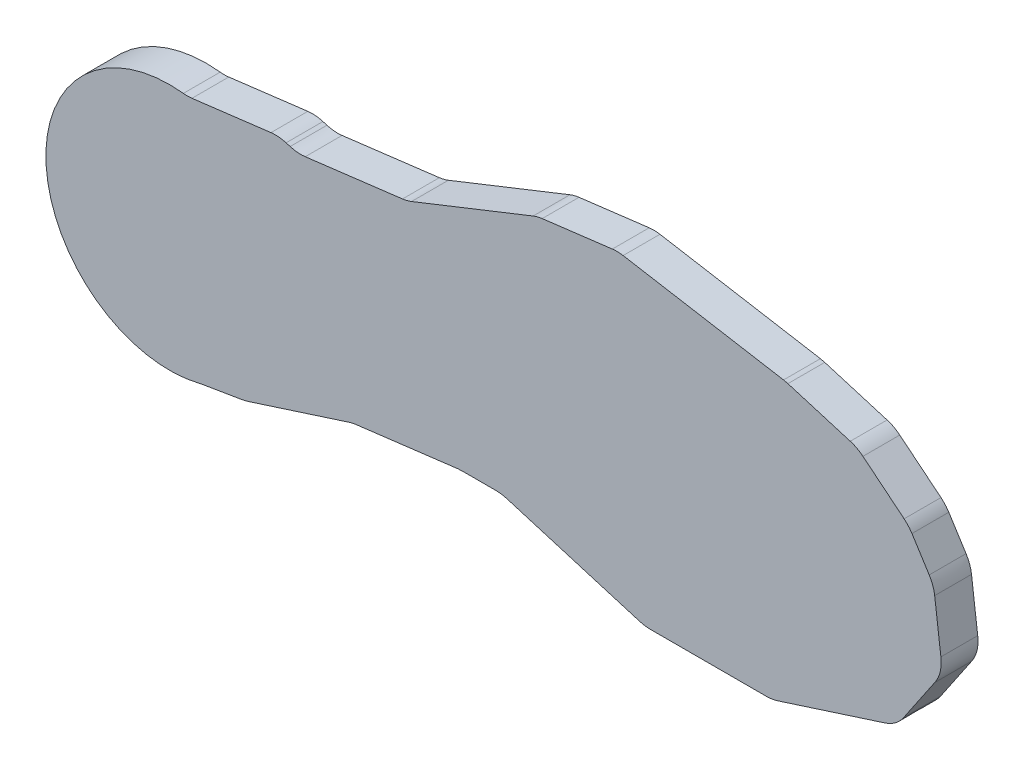
SolidWorks part; units mm, degrees
ref_plane "Front Plane" through (0, 0, 0) normal (0, 0, 1) x (1, 0, 0)
ref_plane "Top Plane" through (0, 0, 0) normal (0, 1, 0) x (1, 0, 0)
ref_plane "Right Plane" through (0, 0, 0) normal (1, 0, 0) x (0, 0, -1)
sketch "Sketch1" plane through (0, 0, 0) normal (0, 0, 1) x (1, 0, 0)
  line L0 (45.8333, 91.5) -> (229.1667, 91.5) construction
  line L1 (52.493, 111.603) -> (77.2786, 114.6756)
  line L2 (77.2786, 114.6756) -> (82.3996, 113.1393)
  line L3 (82.3996, 113.1393) -> (112.1645, 116.8292)
  line L4 (112.1645, 116.8292) -> (147.5386, 130.8579)
  line L5 (147.5386, 130.8579) -> (169.3248, 133.5587)
  line L6 (169.3248, 133.5587) -> (214.9309, 125.7369)
  line L7 (214.9309, 125.7369) -> (234.3436, 119.9131)
  line L8 (234.3436, 119.9131) -> (248.3197, 108.5304)
  line L9 (248.3197, 108.5304) -> (255.0794, 97.8788)
  line L10 (255.0794, 97.8788) -> (257.5, 78.353)
  line L11 (257.5, 78.353) -> (245.0423, 59.9834)
  line L12 (245.0423, 59.9834) -> (211.2437, 49.1269)
  line L13 (211.2437, 49.1269) -> (176.6924, 49.1269)
  line L14 (176.6924, 49.1269) -> (137.7306, 60.8155)
  line L15 (137.7306, 60.8155) -> (126.4401, 60.8155)
  line L16 (126.4401, 60.8155) -> (97.282, 57.2008)
  line L17 (97.282, 57.2008) -> (68.1515, 47.8437)
  line L19 (68.1515, 47.8437) -> (56.1801, 45.8495)
  arc A0 (52.493, 111.603) -> (56.1801, 45.8495) centre (47.6812, 78.353) ccw
sketch "Sketch2" plane through (0, 0, 0) normal (0, 0, 1) x (1, 0, 0)
extrude "Boss-Extrude1" add sketch "Sketch1" along normal blind 10
fillet "Fillet1" radius 10 19 edges at (52.493, 111.603, 5) (77.2786, 114.6756, 5) (82.3996, 113.1393, 5) (112.1645, 116.8292, 5) (147.5386, 130.8579, 5) (169.3248, 133.5587, 5) (214.9309, 125.7369, 5) (234.3436, 119.9131, 5) (248.3197, 108.5304, 5) (255.0794, 97.8788, 5) (257.5, 78.353, 5) (245.0423, 59.9834, 5) (211.2437, 49.1269, 5) (176.6924, 49.1269, 5) (137.7306, 60.8155, 5) (126.4401, 60.8155, 5) (97.282, 57.2008, 5) (68.1515, 47.8437, 5) (56.1801, 45.8495, 5) conic rho 0.5
